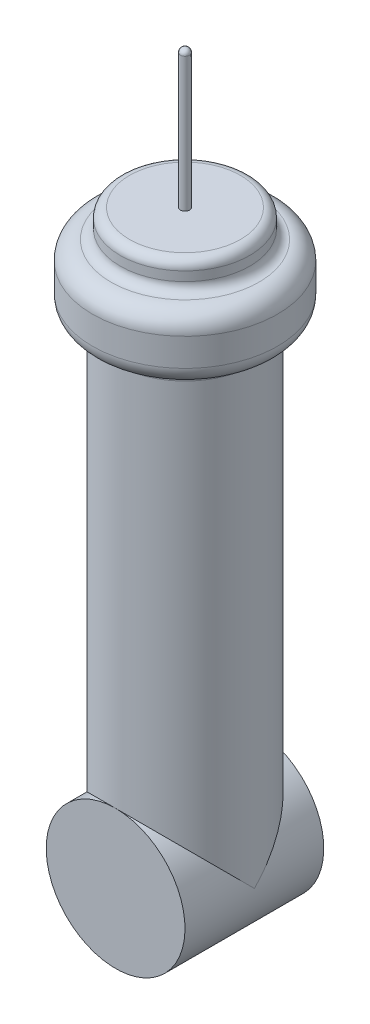
SolidWorks part; units mm, degrees
ref_plane "Front Plane" through (0, 0, 0) normal (0, 0, 1) x (1, 0, 0)
ref_plane "Top Plane" through (0, 0, 0) normal (0, 1, 0) x (1, 0, 0)
ref_plane "Right Plane" through (0, 0, 0) normal (1, 0, 0) x (0, 0, -1)
sketch "Sketch1" plane through (0, 0, 0) normal (0, 0, 1) x (1, 0, 0)
  circle A0 centre (0, 0) radius 15
  dimension "D1" = 30
extrude "Boss-Extrude1" add sketch "Sketch1" along normal blind 30
sketch "Sketch2" plane through (0, 0, 0) normal (0, 1, 0) x (1, 0, 0)
  line L0 (15, 0) -> (-15, 0) construction
  circle A0 centre (0, -15) radius 15
  dimension "D2" = 30
  dimension "D1" = 15
extrude "Boss-Extrude2" add sketch "Sketch2" along normal blind 100
sketch "Sketch3" plane through (0, 100, 0) normal (0, 1, 0) x (1, 0, 0)
  circle A0 centre (0, -15) radius 20
  circle A1 centre (0, -15) radius 15 construction
  dimension "D1" = 0
  dimension "D2" = 40
extrude "Boss-Extrude3" add sketch "Sketch3" along normal blind 14
sketch "Sketch4" plane through (0, 114, 0) normal (0, 1, 0) x (1, 0, 0)
  circle A0 centre (0, -15) radius 14
  circle A1 centre (0, -15) radius 20 construction
  dimension "D1" = 0
  dimension "D2" = 28
extrude "Boss-Extrude4" add sketch "Sketch4" along normal blind 6
sketch "Sketch5" plane through (0, 120, 0) normal (0, 1, 0) x (1, 0, 0)
  circle A0 centre (0, -15) radius 1
  circle A1 centre (0, -15) radius 14 construction
  dimension "D1" = 0
  dimension "D2" = 2
extrude "Boss-Extrude5" add sketch "Sketch5" along normal blind 30
fillet "Fillet1" radius 4 2 edges at (0, 114, 35) (0, 100, 35)
fillet "Fillet2" radius 2 3 edges at (0, 100, 30) (0, 120, 29) (0, 114, 29)
fillet "Fillet3" radius 1 1 edges at (0, 150, 16)
